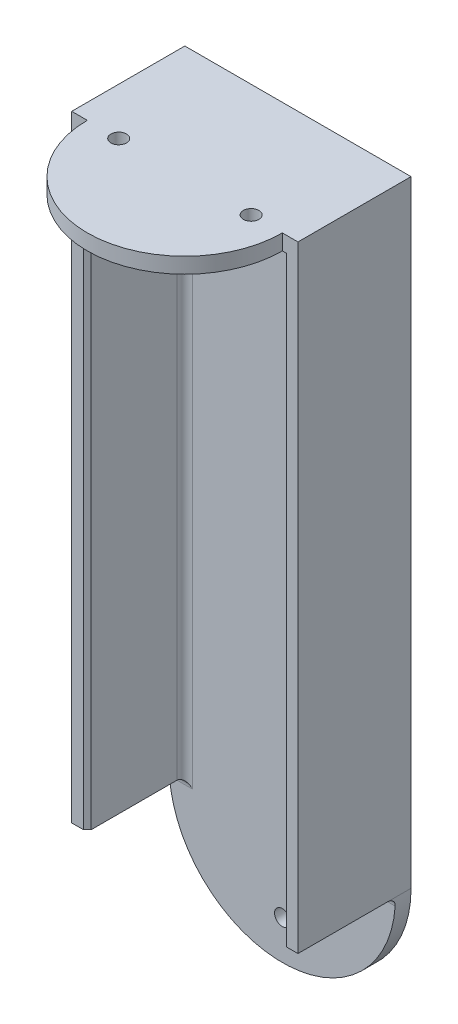
SolidWorks part; units mm, degrees
ref_plane "Plan de face" through (0, 0, 0) normal (0, 0, 1) x (1, 0, 0)
ref_plane "Plan de dessus" through (0, 0, 0) normal (0, 1, 0) x (1, 0, 0)
ref_plane "Plan de droite" through (0, 0, 0) normal (1, 0, 0) x (0, 0, -1)
sketch "Esquisse1" plane through (0, 0, 0) normal (0, 0, 1) x (1, 0, 0)
  line L0 (0, 39.5) -> (0, 34.5) construction
  line L2 (14.5, -39.5) -> (14.5, 39.5)
  line L3 (14.5, 39.5) -> (-14.5, 39.5)
  line L4 (-14.5, -39.5) -> (-14.5, 39.5)
  line L5 (14.5, -39.5) -> (-14.5, 39.5) construction
  line L6 (14.5, 39.5) -> (-14.5, -39.5) construction
  line L7 (0, -54) -> (0, -49) construction
  arc A0 (-14.5, -39.5) -> (14.5, -39.5) centre (0, -39.5) ccw
  circle A1 centre (0, 34.5) radius 1
  circle A2 centre (0, -49) radius 1
  point P0 (0, 0)
  dimension "D1" = 79
  dimension "D2" = 29
extrude "Boss.-Extru.2" add sketch "Esquisse1" against normal blind 2
sketch "Esquisse4" plane through (-14.5, 0, 0) normal (-1, 0, 0) x (0, 0, 1)
  line L1 (0, 39.5) -> (12.5, 39.5)
  line L2 (0, 39.5) -> (0, -39.5)
  line L3 (0, -39.5) -> (12.5, -39.5)
  line L4 (12.5, 39.5) -> (12.5, -39.5)
  point P5 (0, -39.5)
  dimension "D1" = 12.5
extrude "Boss.-Extru.3" add sketch "Esquisse4" against normal blind 2
sketch "Esquisse6" plane through (14.5, 0, 0) normal (1, 0, 0) x (0, 0, -1)
  line L1 (0, 39.5) -> (-12.5, 39.5)
  line L2 (0, 39.5) -> (0, -39.5)
  line L3 (0, -39.5) -> (-12.5, -39.5)
  line L4 (-12.5, 39.5) -> (-12.5, -39.5)
extrude "Boss.-Extru.4" add sketch "Esquisse6" against normal blind 2
sketch "Esquisse11" plane through (0, 39.5, 0) normal (0, 1, 0) x (1, 0, 0)
  line L1 (-12.5, 0) -> (12.5, 0)
  line L2 (-12.5, 0) -> (-12.5, -12.5)
  line L4 (12.5, 0) -> (12.5, -12.5)
  arc A0 (-12.5, -12.5) -> (12.5, -12.5) centre (0, -12.5) ccw
  dimension "D1" = 12.5
extrude "Boss.-Extru.7" add sketch "Esquisse11" against normal blind 2 contours L4 L1 L2 A0
sketch "Esquisse14" plane through (0, 39.5, 0) normal (0, 1, 0) x (1, 0, 0)
  line L0 (-12.5, -12.5) -> (-8.4745, -12.5) construction
  line L1 (12.5, -12.5) -> (8.5, -12.5) construction
  line L2 (0, 2) -> (0, -25) construction
  line L3 (14.5, 2) -> (-14.5, 2) construction
  arc A0 (-12.5, -12.5) -> (12.5, -12.5) centre (0, -12.5) ccw construction
  circle A1 centre (-8.4745, -12.5) radius 1
  circle A2 centre (8.5, -12.5) radius 1
extrude "Enlèv. mat.-Extru.4" cut sketch "Esquisse14" against normal through all contours A1 | A2
chamfer "Chanfrein3" distance 0.5 angle 45 2 edges at (12.5, -1, 12.5) (-12.5, -1, 12.5)
fillet "Congé1" radius 1 5 edges at (13.5, -39.5, 0) (12.5, -1, 0) (0, 37.5, 0) (-12.5, -1, 0) (-13.5, -39.5, 0)
